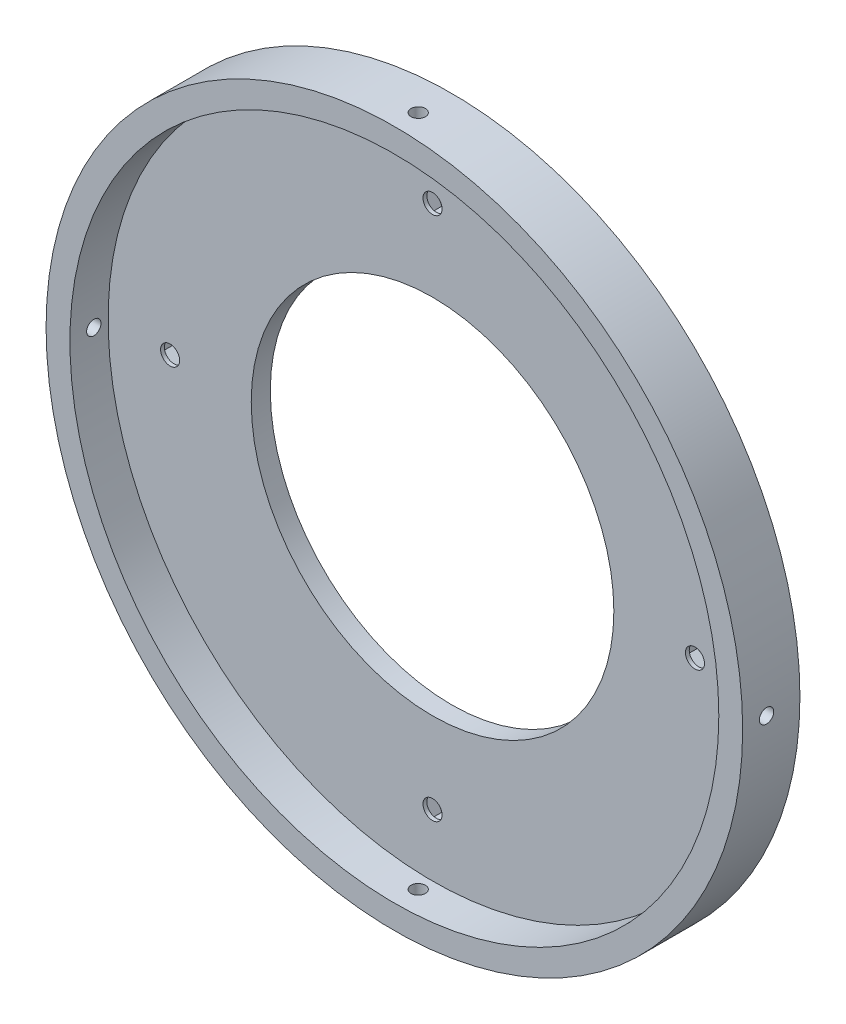
SolidWorks part; units mm, degrees
material "PET"
ref_plane "Front Plane" through (0, 0, 0) normal (0, 0, 1) x (1, 0, 0)
ref_plane "Top Plane" through (0, 0, 0) normal (0, 1, 0) x (1, 0, 0)
ref_plane "Right Plane" through (0, 0, 0) normal (1, 0, 0) x (0, 0, -1)
sketch "Sketch1" plane through (0, 0, 0) normal (0, 0, 1) x (1, 0, 0)
  circle A0 centre (0, 0) radius 73
  circle A1 centre (0, 0) radius 38
  dimension "D1" = 146
  dimension "D2" = 35
extrude "Boss-Extrude1" add sketch "Sketch1" along normal blind 4
sketch "Sketch2" plane through (0, 0, 4) normal (0, 0, 1) x (1, 0, 0)
  circle A0 centre (0, 0) radius 68
  circle A1 centre (0, 0) radius 73
  circle A2 centre (0, 0) radius 73
  dimension "D1" = 0
  dimension "D2" = 5
extrude "Boss-Extrude2" add sketch "Sketch2" along normal blind 8
sketch "Sketch3" plane through (0, 0, 0) normal (0, 1, 0) x (1, 0, 0)
  line L0 (-73, -12) -> (73, -12) construction
  circle A0 centre (0, -7) radius 1.5
  dimension "D2" = 3
  dimension "D1" = 5
extrude "Cut-Extrude1" cut sketch "Sketch3" against normal up to surface (73 mm away) up to face at (73, 0, 0)
pattern_circular "CirPattern1" count 4 over 360 about axis through (0, 0, 4) along (0, 0, -1) of "Cut-Extrude1"
sketch "Sketch9" plane through (0, 0, 0) normal (0, 0, -1) x (-1, 0, 0)
  point P0 (0, 55)
  point P4 (55, 0)
  point P6 (0, -55)
  point P8 (-55, 0)
  dimension "D1" = 55
  dimension "D2" = 0
  dimension "D3" = 55
  dimension "D4" = 55
  dimension "D5" = 55
hole_wizard "Ø4.0mm Dowel Hole1" positions "Sketch9" profile "Sketch10" hole size "Ø4.0" standard "ISO" end condition through all
sketch "Sketch10" plane through (0, 55, 0) normal (1, 0, 0) x (0, 1, 0)
  line L0 (0, 0) -> (0, 12)
  line L1 (0, 12) -> (2, 12)
  line L2 (2, 12) -> (2, 0)
  line L5 (2, 0) -> (0, 0)
  line L11 (0, -6.35) -> (0, 107.95) construction
  dimension "Thru Hole Dia." = 4
  dimension "Thru Hole Depth" = 12
sketch "Sketch13" plane through (0, 0, 0) normal (0, 0, -1) x (-1, 0, 0)
  line L0 (0, 0) -> (55, 0) construction
  line L1 (4.0415, 55) -> (2.0207, 58.5)
  line L2 (2.0207, 58.5) -> (-2.0207, 58.5)
  line L3 (-2.0207, 58.5) -> (-4.0415, 55)
  line L4 (-4.0415, 55) -> (-2.0207, 51.5)
  line L5 (-2.0207, 51.5) -> (2.0207, 51.5)
  line L6 (2.0207, 51.5) -> (4.0415, 55)
  line L7 (55, -4.0415) -> (58.5, -2.0207)
  line L8 (58.5, -2.0207) -> (58.5, 2.0207)
  line L9 (58.5, 2.0207) -> (55, 4.0415)
  line L10 (55, 4.0415) -> (51.5, 2.0207)
  line L11 (51.5, 2.0207) -> (51.5, -2.0207)
  line L12 (51.5, -2.0207) -> (55, -4.0415)
  line L13 (-4.0415, -55) -> (-2.0207, -58.5)
  line L14 (-2.0207, -58.5) -> (2.0207, -58.5)
  line L15 (2.0207, -58.5) -> (4.0415, -55)
  line L16 (4.0415, -55) -> (2.0207, -51.5)
  line L17 (2.0207, -51.5) -> (-2.0207, -51.5)
  line L18 (-2.0207, -51.5) -> (-4.0415, -55)
  line L19 (-55, 4.0415) -> (-58.5, 2.0207)
  line L20 (-58.5, 2.0207) -> (-58.5, -2.0207)
  line L21 (-58.5, -2.0207) -> (-55, -4.0415)
  line L22 (-55, -4.0415) -> (-51.5, -2.0207)
  line L23 (-51.5, -2.0207) -> (-51.5, 2.0207)
  line L24 (-51.5, 2.0207) -> (-55, 4.0415)
  circle A0 centre (0, 55) radius 3.5 construction
  circle A1 centre (55, 0) radius 3.5 construction
  circle A2 centre (0, -55) radius 3.5 construction
  circle A3 centre (-55, 0) radius 3.5 construction
  point P40 (0, 0)
  dimension "D1" = 7
extrude "Cut-Extrude2" cut sketch "Sketch13" against normal blind 3.2
